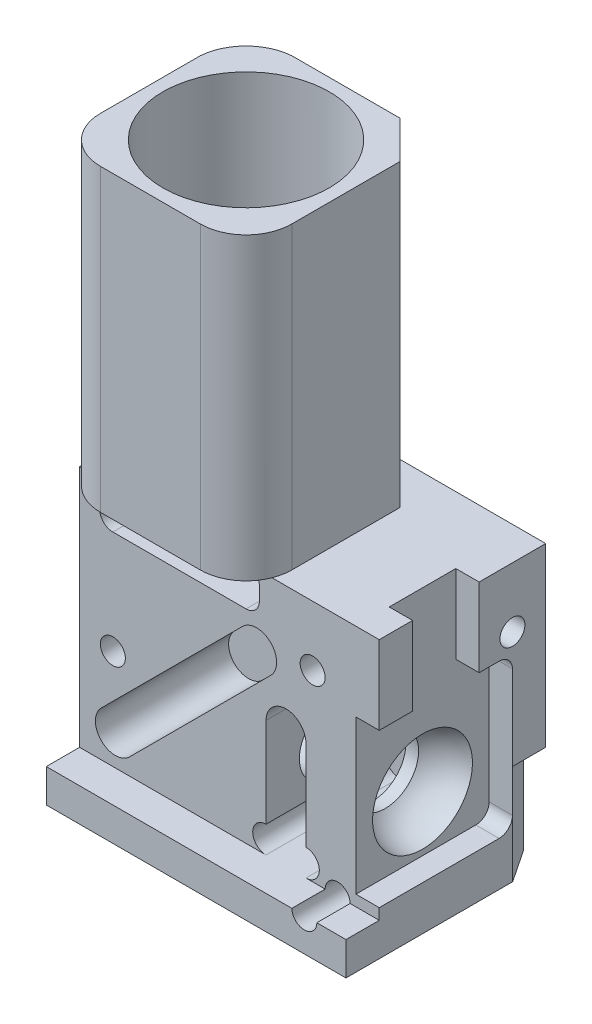
SolidWorks part; units mm, degrees
ref_plane "Front Plane" through (0, 0, 0) normal (0, 0, 1) x (1, 0, 0)
ref_plane "Top Plane" through (0, 0, 0) normal (0, 1, 0) x (1, 0, 0)
ref_plane "Right Plane" through (0, 0, 0) normal (1, 0, 0) x (0, 0, -1)
sketch "Sketch1" plane through (0, 0, 0) normal (0, 1, 0) x (1, 0, 0)
  line L1 (4.5, 3) -> (-4.5, 3)
  line L2 (4.5, 3) -> (4.5, -3)
  line L3 (4.5, -3) -> (-4.5, -3)
  line L4 (-4.5, 3) -> (-4.5, -3)
  line L5 (4.5, 3) -> (-4.5, -3) construction
  line L6 (4.5, -3) -> (-4.5, 3) construction
  point P0 (0, 0)
  dimension "D1" = 6
  dimension "D2" = 9
extrude "Main Body Ext" add sketch "Sketch1" along normal blind 8.3
sketch "Sketch8" plane through (0, 8.3, 0) normal (0, 1, 0) x (1, 0, 0)
  line L0 (0.25, 3) -> (1.5, 1.75)
  line L1 (0.25, 3) -> (-4.5, 3)
  line L2 (1.5, 1.75) -> (1.5, -3)
  line L3 (1.5, -3) -> (-4.5, -3)
  line L4 (-4.5, 3) -> (-4.5, -3)
  line L5 (0.875, 2.375) -> (-4.5, -3) construction
  line L6 (1.5, -3) -> (-4.5, 3) construction
  line L7 (-4.5, 3) -> (-4.5, -3) construction
  line L8 (0, 0) -> (-1.5, 0) construction
  point P0 (-1.5, 0)
  dimension "D1" = 6
  dimension "D2" = 6
  dimension "D3" = 1.25
  dimension "D4" = 3
extrude "Emission Path Ext" add sketch "Sketch8" along normal blind 9
sketch "Sketch3" plane through (0, 0, 0) normal (0, -1, 0) x (1, 0, 0)
  line L0 (-4.5, -3) -> (-4.5, 3) construction
  line L1 (0, 0) -> (-1.5, 0) construction
  circle A0 centre (-1.5, 0) radius 1.25
  dimension "D1" = 3
  dimension "D2" = 2.5
extrude "Emission and Grin Cut" cut sketch "Sketch3" against normal through all
sketch "Sketch4" plane through (4.5, 0, 0) normal (1, 0, 0) x (0, 0, -1)
  line L1 (-3, 0) -> (3, 0) construction
  circle A0 centre (0, 3) radius 1
  dimension "D1" = 2
  dimension "D2" = 3
extrude "Drum Lens Cut" cut sketch "Sketch4" against normal offset from surface (7 mm away) 2 up to face at (-4.5, 8.65, 0)
sketch "Sketch5" plane through (0, 0, 3) normal (0, 0, 1) x (1, 0, 0)
  line L0 (-4.5, 0) -> (4.5, 0) construction
  line L1 (4.5, 8.3) -> (-4.5, 8.3)
  line L2 (4.5, 8.3) -> (4.5, 1)
  line L3 (4.5, 1) -> (-4.5, 1)
  line L4 (-4.5, 8.3) -> (-4.5, 1)
  line L5 (4.5, 8.3) -> (-4.5, 1) construction
  line L6 (4.5, 1) -> (-4.5, 8.3) construction
  line L7 (1.5, 8.3) -> (4.5, 8.3) construction
  line L9 (4.5, 8.3) -> (4.5, 0) construction
  line L10 (-4.5, 17.3) -> (-4.5, 0) construction
  point P0 (0, 4.65)
  dimension "D1" = 1
extrude "FilterSet Cut1" cut sketch "Sketch5" against normal blind 1
sketch "Sketch6" plane through (0, 0, 2) normal (0, 0, 1) x (1, 0, 0)
  line L0 (2.3, 4.5) -> (2.3, 1.8)
  line L1 (1.1, 4.5) -> (2.3, 4.5) construction
  line L2 (2.3, 1) -> (1.1, 1)
  line L3 (-4.5, 1) -> (4.5, 1) construction
  line L4 (-4.5, 8.3) -> (-4.5, 1) construction
  line L5 (-3.9, 7.9) -> (-3.9, 7.5)
  line L6 (1.1, 4.5) -> (1.1, 1.8)
  line L7 (1.5, 8.3) -> (-4.5, 8.3) construction
  line L8 (0.9, 7.9) -> (0.9, 7.5)
  line L9 (-3, 1.5) -> (-3, 1) construction
  line L10 (0.5, 8.3) -> (-3.5, 8.3)
  line L11 (-1.5, 3) -> (-1.5, 1) construction
  line L12 (-1.5, 3) -> (0.4851, 3) construction
  line L13 (0.5, 7.1) -> (-3.5, 7.1)
  line L15 (0.5, 8.3) -> (-3.5, 7.1) construction
  line L16 (0.5, 7.1) -> (-3.5, 8.3) construction
  line L17 (1.1, 1.8) -> (2.3, 1.8) construction
  line L18 (0.3941, 6.5912) -> (-3.8485, 2.3485)
  line L19 (4.5, 1) -> (4.5, 8.3) construction
  line L20 (1.2426, 5.7426) -> (-3, 1.5)
  line L21 (0.3941, 6.5912) -> (-3, 1.5) construction
  line L22 (-3.8485, 2.3485) -> (1.2426, 5.7426) construction
  line L33 (0.5, 8.3) -> (1.102, 8.3) construction
  line L34 (1.102, 8.3) -> (1.102, 7.1) construction
  line L35 (1.102, 7.1) -> (0.5, 7.1) construction
  line L36 (-3.5, 7.1) -> (-4.098, 7.1) construction
  line L37 (-4.098, 7.1) -> (-4.098, 8.3) construction
  line L38 (-4.098, 8.3) -> (-3.5, 8.3) construction
  line L39 (-3.5, 8.3) -> (-2.7284, 6.992) construction
  arc A0 (0.5, 8.3) -> (0.9, 7.9) centre (0.5, 7.9) cw
  arc A1 (1.1, 4.5) -> (2.3, 4.5) centre (1.7, 4.5) cw
  arc A2 (-3.5, 8.3) -> (-3.9, 7.9) centre (-3.5, 7.9) ccw
  arc A3 (0.3941, 6.5912) -> (1.2426, 5.7426) centre (0.8184, 6.1669) cw
  arc A4 (1.1, 1) -> (1.1, 1.8) centre (1.1, 1.4) cw
  arc A5 (-3.8485, 2.3485) -> (-3, 1.5) centre (-3.4243, 1.9243) ccw
  arc A6 (2.3, 1) -> (2.3, 1.8) centre (2.3, 1.4) ccw
  arc A7 (-3.5, 7.1) -> (-3.9, 7.5) centre (-3.5, 7.5) cw
  arc A8 (0.5, 7.1) -> (0.9, 7.5) centre (0.5, 7.5) ccw
  point P5 (-1.5, 7.7)
  point P10 (-1.3029, 4.0456)
  dimension "D10" = 0.5
  dimension "D5" = 2.2
  dimension "D8" = 0.4
  dimension "D11" = 0.4
  dimension "D12" = 0.4
  dimension "D1" = 1.2
  dimension "D2" = 45
  dimension "D3" = 3.5
  dimension "D4" = 1.2
  dimension "D6" = 2
  dimension "D7" = 4
  dimension "D9" = 3
  dimension "D13" = 1.2
  dimension "D14" = 3
  dimension "D15" = 6
extrude "FilterSet Cut2" cut sketch "Sketch6" against normal offset from surface (4 mm away) 1 up to face at (0.4375, 9.2833, -3)
sketch "Sketch10" plane through (0, 17.3, 0) normal (0, 1, 0) x (1, 0, 0)
  line L0 (-1.5, 0) -> (-1.5, -3) construction
  line L1 (-4.5, -3) -> (1.5, -3) construction
  line L3 (-1.5, 0) -> (-4.5, 0) construction
  line L4 (-4.5, 3) -> (-4.5, -3) construction
  circle A0 centre (-1.5, 0) radius 2.5
  dimension "D1" = 5
extrude "Emission Lens Cut" cut sketch "Sketch10" against normal offset from surface (8.5 mm away) 0.5 up to face at (-1.125, 8.3, 1.3125)
sketch "Sketch12" plane through (4.5, 0, 0) normal (1, 0, 0) x (0, 0, -1)
  line L0 (0, 3.635) -> (0, 0) construction
  line L1 (1.6, 5.94) -> (-1.6, 5.94)
  line L2 (1.6, 5.94) -> (1.6, 1.33) construction
  line L3 (-2, 1.33) -> (1.6, 1.33)
  line L4 (-1.6, 5.94) -> (-1.6, 1.33) construction
  line L5 (1.6, 5.94) -> (-1.6, 1.33) construction
  line L6 (1.6, 1.33) -> (-1.6, 5.94) construction
  line L7 (-3, 0) -> (3, 0) construction
  line L9 (-1.6, 5.94) -> (-2, 5.94)
  line L10 (-2, 1) -> (-2, 8.3) construction
  line L11 (-2, 5.94) -> (-2, 1.33)
  line L12 (2, 5.54) -> (2, 1.73)
  arc A1 (1.6, 5.94) -> (2, 5.54) centre (1.6, 5.54) cw
  arc A2 (1.6, 1.33) -> (2, 1.73) centre (1.6, 1.73) ccw
  circle A3 centre (0, 3) radius 1 construction
  point P0 (0, 3.635)
  dimension "D2" = 4.61
  dimension "D3" = 1.67
  dimension "D1" = 3.2
  dimension "D4" = 0.4
sketch "Sketch15" plane through (0, 0, 0) normal (0, -1, 0) x (1, 0, 0)
  line L0 (-3.25, 1.875) -> (-3.25, -1.875) construction
  line L2 (1.5, 0) -> (-1.5, 0) construction
  line L3 (-1.5, 0) -> (-3.25, 0) construction
  circle A0 centre (-3.25, -1.875) radius 0.795
  circle A1 centre (-3.25, 1.875) radius 0.795
  circle A2 centre (1.5, 0) radius 0.795
  dimension "D4" = 1.59
  dimension "D1" = 3.75
  dimension "D2" = 3
  dimension "D3" = 1.75
extrude "Magnets Cut" cut sketch "Sketch15" against normal blind 0.9
sketch "Sketch18" plane through (0, 0, 2) normal (0, 0, 1) x (1, 0, 0)
  line L0 (-4.5, 8.3) -> (-4.5, 1) construction
  line L1 (4.5, 1) -> (4.5, 8.3) construction
  line L2 (4.5, 8.3) -> (1.5, 8.3) construction
  line L3 (-4.5, 0) -> (4.5, 0) construction
  line L7 (-4.5, 1) -> (1.1, 1) construction
  line L9 (-4.5, 1) -> (-4.5, 0) construction
  circle A0 centre (-3.5, 4) radius 0.375
  circle A1 centre (2.5, 6.5) radius 0.375
  circle A2 centre (3.25, 1) radius 0.375
  dimension "D1" = 0.75
  dimension "D2" = 1
  dimension "D3" = 1.8
  dimension "D4" = 2
  dimension "D5" = 3
  dimension "D6" = 1
  dimension "D7" = 7.75
extrude "Screw Holes Cut" cut sketch "Sketch18" against normal blind 3 and the other way through all
fillet "External Fillet 1" radius 1.5 2 edges at (-4.5, 8.65, -3)
sketch "Sketch14" plane through (0, 0, 0) normal (0, -1, 0) x (1, 0, 0)
  line L0 (4.5, -3) -> (4.5, -2.0067)
  line L1 (4.5, 3) -> (4.5, -3) construction
  line L2 (4.5, -2.0067) -> (3.8378, -3)
  line L3 (4.5, -3) -> (-3, -3) construction
  line L4 (3.8378, -3) -> (4.5, -3)
  line L5 (4.5, -3) -> (-4.5, 3) construction
  line L6 (-4.5, -1.5) -> (-4.5, 3) construction
  line L7 (-4.5, 3) -> (4.5, 3) construction
  dimension "D1" = 1.1938
sketch "Sketch28" plane through (0, 7.1, 0) normal (0, 1, 0) x (1, 0, 0)
  circle A0 centre (-1.5, 0) radius 1.5
  dimension "D1" = 3
extrude "Cut-Extrude8" cut sketch "Sketch28" against normal blind 4 and the other way through all
extrude "Cut-Extrude9" cut sketch "Sketch14" against normal blind 3
extrude "Cut-Extrude10" cut sketch "Sketch12" against normal blind 0.7
sketch "Sketch29" plane through (4.5, 0, 0) normal (1, 0, 0) x (0, 0, -1)
  line L0 (3, 8.3) -> (3, 3) construction
  line L1 (-2, 8.3) -> (3, 8.3) construction
  circle A0 centre (2, 6.5) radius 0.375
  dimension "D1" = 0.75
  dimension "D2" = 1
  dimension "D3" = 1.8
extrude "Cut-Extrude11" cut sketch "Sketch29" against normal blind 2.5
sketch "Sketch31" plane through (3.8, 0, 0) normal (1, 0, 0) x (0, 0, -1)
  circle A0 centre (0, 3) radius 1.6
  dimension "D1" = 3.2
sketch "Sketch32" plane through (4.5, 0, 0) normal (1, 0, 0) x (0, 0, -1)
  line L0 (-2, 8.3) -> (3, 8.3) construction
  line L1 (-1, 8.3) -> (1, 8.3)
  line L2 (-1, 8.3) -> (-1, 5.94)
  line L3 (-1, 5.94) -> (1, 5.94)
  line L4 (1, 8.3) -> (1, 5.94)
  line L5 (1.6, 5.94) -> (-2, 5.94) construction
  line L6 (-2, 5.94) -> (-2, 8.3) construction
  line L8 (3, 8.3) -> (3, 3) construction
  dimension "D1" = 1
  dimension "D2" = 2
extrude "Cut-Extrude14" cut sketch "Sketch32" against normal up to surface (0.7 mm away) up to face at (3.8, 3.635, -0.5609)
sketch "Sketch33" plane through (0, 0, 0) normal (0, 0, 1) x (1, 0, 0)
  line L0 (3.8, 3) -> (2.3, 3)
  line L1 (3.8, 1.4) -> (3.8, 4.6) construction
  line L2 (3.8, 3) -> (3.8, 4.5)
  arc A0 (2.3, 3) -> (3.8, 4.5) centre (3.8, 3) cw
  dimension "D2" = 1.5
revolve "Cut-Revolve1" cut sketch "Sketch33" angle 360 about L0
sketch "Sketch36" plane through (0, 17.3, 0) normal (0, 1, 0) x (1, 0, 0)
  line L0 (-4.5, -1.5) -> (-4.5, -3)
  line L1 (-4.5, 1.5) -> (-4.5, -3) construction
  line L2 (-4.5, -3) -> (-3, -3)
  line L3 (-4.5, -3) -> (0, -3) construction
  arc A0 (-4.5, -1.5) -> (-3, -3) centre (-3, -1.5) ccw
  dimension "D1" = 1.5
  dimension "D2" = 1.5
extrude "Cut-Extrude16" cut sketch "Sketch36" against normal up to surface (9 mm away) up to face at (-1.3971, 8.3, 1.2781)
sketch "Sketch37" plane through (0, 8.8, 0) normal (0, 1, 0) x (1, 0, 0)
  circle A0 centre (-1.5, 0) radius 2
  circle A1 centre (-1.5, 0) radius 1.5 construction
  dimension "D1" = 4
extrude "Cut-Extrude17" cut sketch "Sketch37" against normal up to next
sketch "Sketch38" plane through (0, 17.3, 0) normal (0, 1, 0) x (1, 0, 0)
  line L0 (-4.375, -1.5) -> (-4.375, 1.5)
  line L1 (1.375, 1.75) -> (1.375, -1.5)
  line L2 (-3, -2.875) -> (0, -2.875)
  line L3 (1.375, 1.75) -> (0.25, 2.875)
  line L4 (0.25, 2.875) -> (-3, 2.875)
  line L5 (0.25, 3) -> (-3, 3) construction
  line L6 (-4.5, 1.5) -> (-4.5, -1.5) construction
  line L7 (-3, -3) -> (0, -3) construction
  line L8 (1.5, -1.5) -> (1.5, 1.75) construction
  line L9 (1.5, 1.75) -> (0.25, 3) construction
  line L10 (-3, 3) -> (0.25, 3)
  line L11 (0.25, 3) -> (1.5, 1.75)
  line L12 (1.5, 1.75) -> (1.5, -1.5)
  line L13 (0, -3) -> (-3, -3)
  line L14 (-4.5, -1.5) -> (-4.5, 1.5)
  arc A0 (1.375, -1.5) -> (0, -2.875) centre (0, -1.5) cw
  arc A1 (-3, 2.875) -> (-4.375, 1.5) centre (-2.8798, 1.3798) ccw
  arc A2 (-3, -2.875) -> (-4.375, -1.5) centre (-3, -1.5) cw
  arc A3 (-4.5, -1.5) -> (-3, -3) centre (-3, -1.5) ccw construction
  arc A4 (0, -3) -> (1.5, -1.5) centre (0, -1.5) ccw construction
  arc A5 (-4.5, 1.5) -> (-3, 3) centre (-3, 1.5) cw
  arc A6 (1.5, -1.5) -> (0, -3) centre (0, -1.5) cw
  arc A7 (-3, -3) -> (-4.5, -1.5) centre (-3, -1.5) cw
  dimension "D2" = 1.5
  dimension "D1" = 0.125
extrude "Cut-Extrude18" cut sketch "Sketch38" against normal up to surface (9 mm away) contours A2 L0 A1 L4 L3 L1 A0 L2 | A7 L14 A5 L10 L11 L12 A6 L13 up to face at (3.3036, 8.3, 0.0004)
